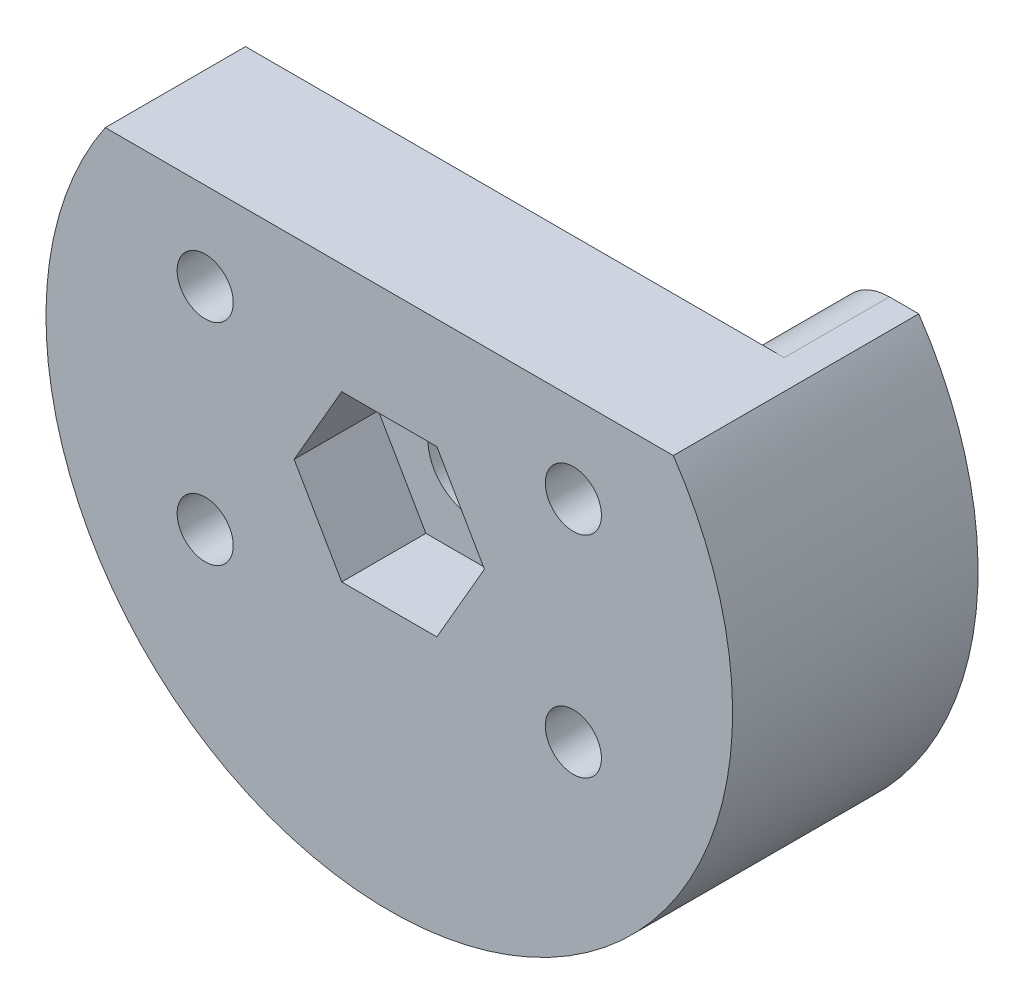
SolidWorks part; units mm, degrees
ref_plane "Front Plane" through (0, 0, 0) normal (0, 0, 1) x (1, 0, 0)
ref_plane "Top Plane" through (0, 0, 0) normal (0, 1, 0) x (1, 0, 0)
ref_plane "Right Plane" through (0, 0, 0) normal (1, 0, 0) x (0, 0, -1)
sketch "Sketch1" plane through (0, 0, 0) normal (0, 0, 1) x (1, 0, 0)
  line L0 (0, 0) -> (0, 12.5) construction
  line L1 (16.2, 12.5) -> (16.2, 0) construction
  line L2 (0, 0) -> (16.2, 0) construction
  line L3 (0, 12.5) -> (16.2, 12.5)
  line L4 (2.85, 4) -> (13.35, 10) construction
  arc A0 (0, 12.5) -> (16.2, 12.5) centre (8.1, 7) ccw
  circle A4 centre (2.85, 10) radius 0.8
  circle A5 centre (13.35, 10) radius 0.8
  circle A6 centre (13.35, 4) radius 0.8
  circle A7 centre (2.85, 4) radius 0.8
  point P1 (8.1, -2.7908)
  dimension "D11" = 1.6
  dimension "D1" = 2.85
  dimension "D2" = 4
  dimension "D3" = 4
  dimension "D4" = 2.85
  dimension "D5" = 6
  dimension "D6" = 6
  dimension "D7" = 2.85
  dimension "D8" = 2.85
  dimension "D9" = 2.5
  dimension "D10" = 15.2908
extrude "Boss-Extrude1" add sketch "Sketch1" along normal blind 4
sketch "Sketch2" plane through (0, 0, 4) normal (0, 0, 1) x (1, 0, 0)
  line L0 (2.85, 10) -> (13.35, 4) construction
  line L1 (2.85, 4) -> (13.35, 10) construction
  line L2 (10.8135, 7) -> (9.4568, 9.35)
  line L3 (9.4568, 9.35) -> (6.7432, 9.35)
  line L4 (6.7432, 9.35) -> (5.3865, 7)
  line L5 (5.3865, 7) -> (6.7432, 4.65)
  line L6 (6.7432, 4.65) -> (9.4568, 4.65)
  line L7 (9.4568, 4.65) -> (10.8135, 7)
  circle A1 centre (8.1, 7) radius 2.35 construction
  dimension "D2" = 4.7
extrude "Cut-Extrude1" cut sketch "Sketch2" against normal blind 2.4
sketch "Sketch3" plane through (0, 0, 4) normal (0, 0, 1) x (1, 0, 0)
  line L0 (2.85, 10) -> (13.35, 4) construction
  circle A0 centre (8.1, 7) radius 1.3
  dimension "D1" = 2.6
extrude "Cut-Extrude2" cut sketch "Sketch3" against normal up to surface (4 mm away) up to face at (8.1, 4.8546, 0)
sketch "Sketch4" plane through (0, 0, 0) normal (0, 0, 1) x (1, 0, 0)
  line L0 (16.2, 12.5) -> (0, 12.5) construction
  line L1 (8.1, 12.5) -> (8.1, 7) construction
  line L2 (16.2, 12.5) -> (0, 12.5) construction
  line L3 (16.2, 12.5) -> (15.3621, 12.5)
  line L4 (1.69, 9.242) -> (-1.4307, 9.242)
  arc A0 (15.3621, 12.5) -> (14.0482, 10.2763) centre (15.3621, 11) ccw
  arc A1 (0, 12.5) -> (16.2, 12.5) centre (8.1, 7) ccw construction
  circle A2 centre (0.8379, 11) radius 1.5 construction
  arc A3 (1.69, 9.242) -> (14.0482, 10.2763) centre (8.1, 7) ccw
  arc A4 (-1.4307, 9.242) -> (16.2, 12.5) centre (8.1, 7) ccw
extrude "Boss-Extrude2" add sketch "Sketch4" against normal blind 3
